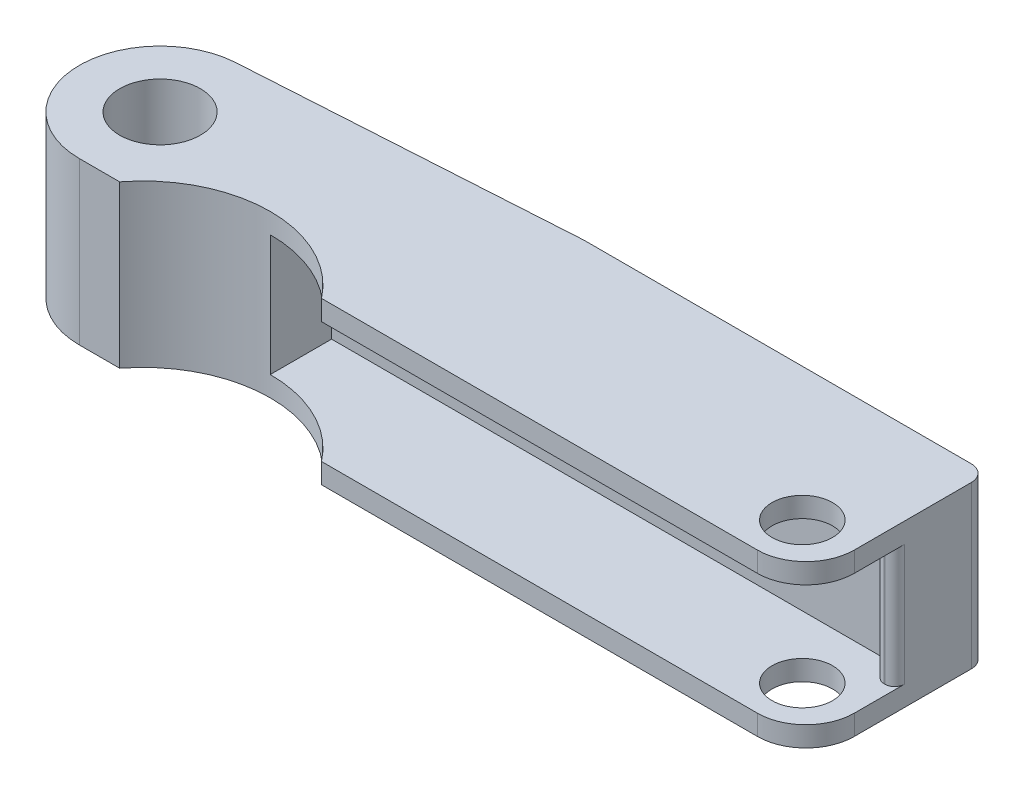
SolidWorks part; units mm, degrees
ref_plane "Front Plane" through (0, 0, 0) normal (0, 0, 1) x (1, 0, 0)
ref_plane "Top Plane" through (0, 0, 0) normal (0, 1, 0) x (1, 0, 0)
ref_plane "Right Plane" through (0, 0, 0) normal (1, 0, 0) x (0, 0, -1)
sketch "Sketch1" plane through (0, 0, 0) normal (0, 1, 0) x (1, 0, 0)
  line L1 (0, 0) -> (127, 0)
  line L2 (0, 0) -> (0, 28.575)
  line L3 (0, 28.575) -> (127, 28.575)
  line L4 (127, 0) -> (127, 28.575)
  dimension "D1" = 127
  dimension "D2" = 28.575
extrude "Boss-Extrude1" add sketch "Sketch1" along normal blind 25.4
sketch "Sketch5" plane through (0, 25.4, 0) normal (0, 1, 0) x (1, 0, 0)
  line L0 (0, 0) -> (19.05, 0)
  line L1 (0, 0) -> (127, 0) construction
  line L2 (50.8, 0) -> (19.05, 0)
  arc A0 (19.05, 0) -> (50.8, 0) centre (34.925, -12.2118) cw
  line M5 (0, 0) -> (127, 0)
  dimension "D2" = 31.75
  dimension "D1" = 19.05
extrude "Cut-Extrude3" cut sketch "Sketch5" along normal blind 45.72 and the other way blind 55.88 contours A0 M5 region at (34.925, 25.4, -3.1857)
fillet "Fillet1" radius 12.7 2 edges at (0, 12.7, 0) (0, 12.7, -28.575)
sketch "Sketch6" plane through (0, 25.4, 0) normal (0, 1, 0) x (1, 0, 0)
  arc A1 (12.7, 28.575) -> (0, 15.875) centre (12.7, 15.875) ccw construction
  arc A2 (12.7, 28.575) -> (0, 15.875) centre (12.7, 15.875) ccw
  arc A4 (0, 12.7) -> (12.7, 0) centre (12.7, 12.7) ccw construction
  arc A5 (0, 12.7) -> (12.7, 0) centre (12.7, 12.7) ccw
  circle A6 centre (12.7, 12.7) radius 6.35
extrude "Cut-Extrude5" cut sketch "Sketch6" against normal blind 31.75 contours A6
sketch "Sketch7" plane through (0, 25.4, 0) normal (0, 1, 0) x (1, 0, 0)
  line L0 (127, 28.575) -> (63.5, 28.575)
  line L1 (127, 28.575) -> (12.7, 28.575) construction
  line L2 (63.5, 28.575) -> (11.9139, 25.3756)
  line L3 (0, 15.875) -> (0, 12.7) construction
  line L4 (0, 15.875) -> (0, 12.7)
  line L5 (127, 28.575) -> (12.7, 28.575)
  circle A0 centre (12.7, 12.7) radius 12.7
  arc A1 (12.7, 28.575) -> (0, 15.875) centre (12.7, 15.875) ccw construction
  arc A2 (12.7, 28.575) -> (0, 15.875) centre (12.7, 15.875) ccw
  line M4 (0, 15.875) -> (0, 12.7)
  line M10 (127, 28.575) -> (12.7, 28.575)
  arc M11 (12.7, 28.575) -> (0, 15.875) centre (12.7, 15.875) ccw
  dimension "D1" = 25.4
extrude "Cut-Extrude6" cut sketch "Sketch7" against normal blind 31.75 contours A0 L2 M10 M11 M4 region at (21.8327, 25.4, -26.4317)
sketch "Sketch8" plane through (0, 0, 0) normal (0, 0, 1) x (1, 0, 0)
  line L0 (127, 25.4) -> (127, 0) construction
  line L1 (123.825, 22.225) -> (34.925, 22.225)
  line L2 (123.825, 22.225) -> (123.825, 3.175)
  line L3 (123.825, 3.175) -> (34.925, 3.175)
  line L4 (34.925, 22.225) -> (34.925, 3.175)
  line L5 (50.8, 25.4) -> (127, 25.4) construction
  line L6 (50.8, 0) -> (127, 0) construction
  dimension "D1" = 3.175
  dimension "D2" = 88.9
  dimension "D3" = 3.175
  dimension "D4" = 3.175
extrude "Cut-Extrude7" cut sketch "Sketch8" against normal blind 17.4625
fillet "Fillet2" radius 7.62 1 edges at (127, 12.7, 0)
sketch "Sketch10" plane through (0, 0, 0) normal (0, -1, 0) x (1, 0, 0)
  arc A0 (127, -7.62) -> (119.38, 0) centre (119.38, -7.62) ccw construction
  arc A1 (127, -7.62) -> (119.38, 0) centre (119.38, -7.62) ccw
  circle A2 centre (118.8206, -7.62) radius 4.7625
  dimension "D1" = 9.525
extrude "Cut-Extrude8" cut sketch "Sketch10" against normal blind 42.8625 contours A2 region at (118.8206, 0, -7.62)
sketch "Sketch11" plane through (127, 0, 0) normal (1, 0, 0) x (0, 0, -1)
  line L0 (1.4308, 3.175) -> (1.4308, 22.225) construction
  line L1 (7.62, 25.4) -> (7.62, 0) construction
  line L2 (1.4308, 3.175) -> (1.4308, 22.225)
  line L3 (7.62, 25.4) -> (7.62, 22.225)
  line L4 (7.62, 3.175) -> (7.62, 0)
  line L5 (1.4308, 3.175) -> (7.62, 3.175)
  line L6 (1.4308, 3.175) -> (1.4308, 22.225)
  line L7 (1.4308, 22.225) -> (7.62, 22.225)
  line L9 (7.62, 3.175) -> (13.97, 3.175)
  line L11 (7.62, 22.225) -> (13.97, 22.225)
  line L12 (13.97, 3.175) -> (13.97, 22.225)
  line L13 (7.62, 3.175) -> (7.62, 22.225)
  line M2 (7.62, 25.4) -> (7.62, 0)
  dimension "D1" = 6.35
extrude "Cut-Extrude10" cut sketch "Sketch11" against normal blind 8.0645 contours L7 L2 L5 M2 | L9 L12 L11 M2 region at (127, 12.7, -4.5254) region at (127, 12.7, -10.795)
fillet "Fillet3" radius 1.524 3 edges at (127, 12.7, -13.97) (123.825, 12.7, -13.97) (123.825, 12.7, -17.4625)
fillet "Fillet4" radius 2.54 1 edges at (127, 12.7, -28.575)
